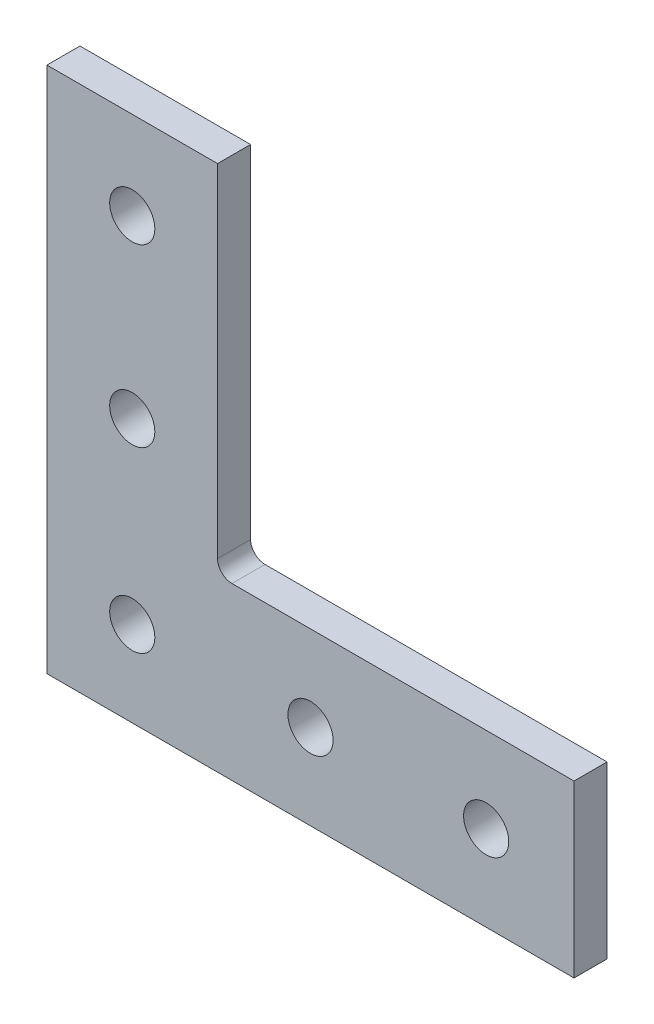
SolidWorks part; units mm, degrees
ref_plane "Front Plane" through (0, 0, 0) normal (0, 0, 1) x (1, 0, 0)
ref_plane "Top Plane" through (0, 0, 0) normal (0, 1, 0) x (1, 0, 0)
ref_plane "Right Plane" through (0, 0, 0) normal (1, 0, 0) x (0, 0, -1)
sketch "Sketch1" plane through (0, 0, 0) normal (0, 0, 1) x (1, 0, 0)
  line L0 (-38.1, -38.1) -> (-38.1, 38.1) construction
  line L1 (38.1, -38.1) -> (-38.1, -38.1) construction
  line L2 (-38.1, 38.1) -> (-13.4366, 38.1) construction
  line L3 (-29.0322, 25.4) -> (-22.5044, 25.4) construction
  point P0 (-25.7683, 38.1)
  point P3 (-25.7683, 0)
  point P4 (-38.1, 0)
  point P6 (-38.1, 38.1)
  point P8 (-38.1, 0)
  point P10 (0, 0)
  point P12 (0, -38.1)
  point P14 (-25.7683, 25.4)
  dimension "Length" = 76.2
  dimension "Width" = 24.6634
  dimension "Hole to Edge" = 12.7
  dimension "Hole Spacing" = 25.4
  dimension "Hole Dia" = 6.5278
sketch "Sketch2" plane through (0, 0, 0) normal (1, 0, 0) x (0, 0, -1)
  line L0 (2.3876, 0) -> (-2.3876, 0) construction
  point P4 (0, 0)
  dimension "Thickness" = 4.7752
sketch "Sketch3" plane through (0, 0, 0) normal (0, 0, 1) x (1, 0, 0)
  line L0 (-13.4366, 38.1) -> (-38.1, 38.1)
  line L1 (-38.1, 38.1) -> (-38.1, -38.1)
  line L2 (-38.1, -38.1) -> (38.1, -38.1)
  line L3 (38.1, -38.1) -> (38.1, -13.4366)
  line L4 (38.1, -13.4366) -> (-11.3538, -13.4366)
  line L5 (-13.4366, -11.3538) -> (-13.4366, 38.1)
  arc A0 (-11.3538, -13.4366) -> (-13.4366, -11.3538) centre (-11.3538, -11.3538) cw
  dimension "Radius" = 2.0828
extrude "Boss-Extrude1" add sketch "Sketch3" against normal up to vertex (2.3876 mm away) and the other way up to vertex (2.3876 mm away) up to point (0, 0, -2.3876) other way up to point (0, 0, 2.3876)
sketch "Sketch4" plane through (0, 0, 2.3876) normal (0, 0, 1) x (1, 0, 0)
  line L0 (-29.0322, 25.4) -> (-22.5044, 25.4) construction
  line L1 (-38.1, -38.1) -> (0, 0) construction
  circle A0 centre (-25.7683, 25.4) radius 3.2639
  circle A1 centre (-25.7683, 0) radius 3.2639
  circle A3 centre (0, -25.7683) radius 3.2639
  circle A4 centre (25.4, -25.7683) radius 3.2639
  circle A5 centre (-25.7683, -25.7683) radius 3.2639
extrude "Cut-Extrude1" cut sketch "Sketch4" against normal through all both and the other way through all
ref_plane "Plane1" through (0, -25.7683, 0) normal (0, 1, 0) x (1, 0, 0)
ref_plane "Plane2" through (-25.7683, 0, 0) normal (-1, 0, 0) x (0, 0, 1)
